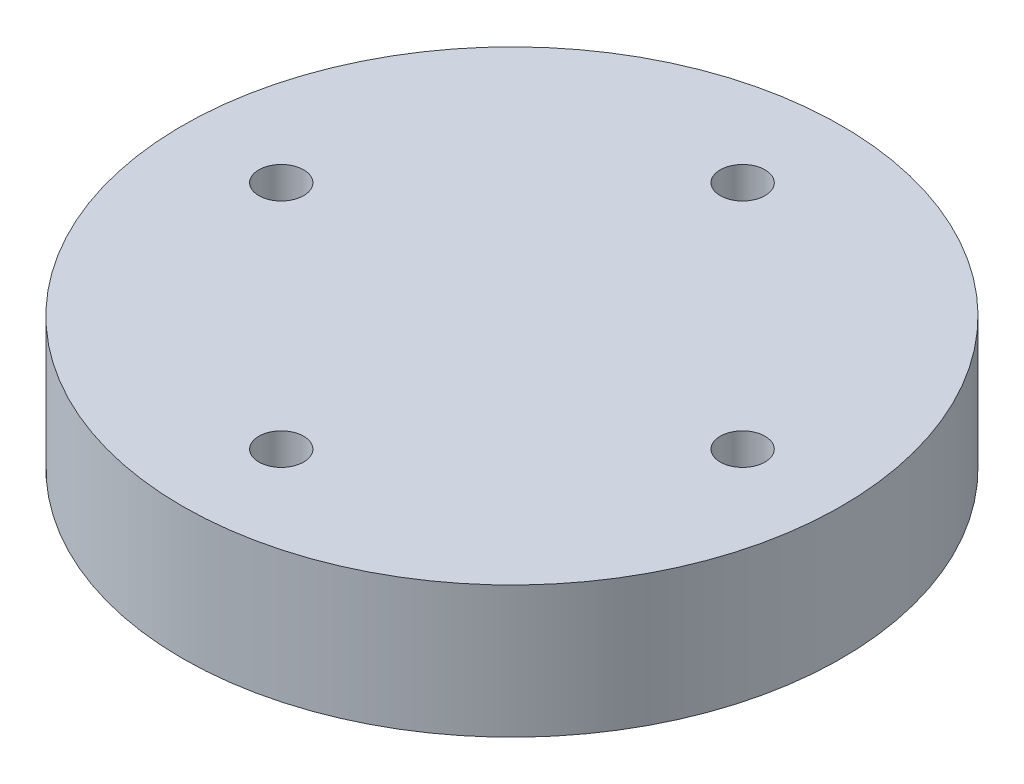
SolidWorks part; units mm, degrees
ref_plane "Ebene vorne" through (0, 0, 0) normal (0, 0, 1) x (1, 0, 0)
ref_plane "Ebene oben" through (0, 0, 0) normal (0, 1, 0) x (1, 0, 0)
ref_plane "Ebene rechts" through (0, 0, 0) normal (1, 0, 0) x (0, 0, -1)
sketch "Skizze1" plane through (0, 0, 0) normal (0, 1, 0) x (1, 0, 0)
  circle A0 centre (0, 0) radius 25
  dimension "D1" = 50
extrude "Aufsatz-Linear austragen1" add sketch "Skizze1" along normal blind 10
sketch "Skizze2" plane through (0, 0, 0) normal (0, -1, 0) x (1, 0, 0)
  circle A0 centre (0, 0) radius 11
  circle A1 centre (0, 0) radius 13
  dimension "D1" = 22
  dimension "D2" = 26
extrude "Aufsatz-Linear austragen2" add sketch "Skizze2" along normal blind 2
sketch "Skizze3" plane through (0, 0, 0) normal (0, 1, 0) x (1, 0, 0)
  circle A0 centre (0, 0) radius 11
  dimension "D1" = 22
extrude "Schnitt-Linear austragen1" cut sketch "Skizze3" along normal blind 8
chamfer "Fase1" distance 1 angle 45 1 edges at (0, -2, -13)
sketch "Skizze4" plane through (0, 0, 0) normal (0, -1, 0) x (1, 0, 0)
  circle A0 centre (0, 0) radius 17.5 construction
  circle A1 centre (0, 17.5) radius 1.7
  dimension "D1" = 35
  dimension "D2" = 3.4
extrude "Schnitt-Linear austragen2" cut sketch "Skizze4" against normal through all
pattern_circular "Kreismuster1" count 4 over 360 about axis through (0, 10, 0) along (0, -1, 0) of "Schnitt-Linear austragen2"
